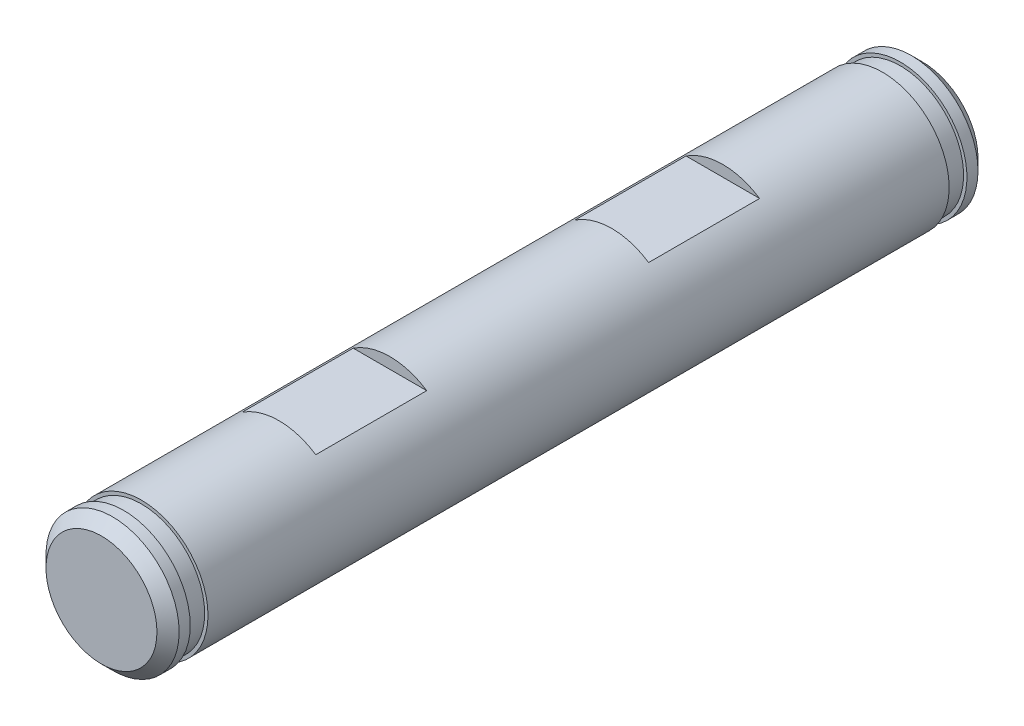
SolidWorks part; units mm, degrees
other "Uwaga1"
sketch "Szkic5" plane through (-3, 3, 37) normal (-0.9422, 0.1287, 0.3092) x (0.3037, -0.0607, 0.9508)
material "Stop 1060"
ref_plane "Płaszczyzna przednia" through (0, 0, 0) normal (0, 0, 1) x (1, 0, 0)
ref_plane "Płaszczyzna górna" through (0, 0, 0) normal (0, 1, 0) x (1, 0, 0)
ref_plane "Płaszczyzna prawa" through (0, 0, 0) normal (1, 0, 0) x (0, 0, -1)
sketch "Szkic1" plane through (0, 0, 0) normal (0, 0, 1) x (1, 0, 0)
  circle A0 centre (0, 0) radius 3
  dimension "D1" = 6
extrude "Dodanie-wyciągnięcie1" add sketch "Szkic1" along normal blind 37
chamfer "Sfazowanie1" distance 0.5 angle 45 2 edges at (3, 0, 0) (3, 0, 37)
sketch "Szkic2" plane through (0, 0, 37) normal (0, 0, 1) x (1, 0, 0)
  circle A0 centre (0, 0) radius 3
  circle A1 centre (0, 0) radius 2.85
  dimension "D1" = 6
  dimension "D2" = 5.7
extrude "Wytnij-wyciągnięcie1" cut sketch "Szkic2" against normal blind 0.8 from offset 1 offset against normal yes
sketch "Szkic3" plane through (0, 0, 0) normal (0, 0, -1) x (-1, 0, 0)
  circle A0 centre (0, 0) radius 3
  circle A1 centre (0, 0) radius 2.85
  dimension "D1" = 5.7
  dimension "D2" = 6
extrude "Wytnij-wyciągnięcie2" cut sketch "Szkic3" against normal blind 0.8 from offset 1 offset against normal yes
sketch "Szkic4" plane through (0, 0, 37) normal (0, 0, 1) x (1, 0, 0)
  line L0 (-1.6583, 2.5) -> (1.6583, 2.5)
  arc A0 (1.6583, 2.5) -> (-1.6583, 2.5) centre (0, 0) ccw
  dimension "D1" = 6
  dimension "D2" = 2.5
extrude "Wytnij-wyciągnięcie3" cut sketch "Szkic4" along normal blind 5 from offset 13 offset against normal yes
extrude "Wytnij-wyciągnięcie4" cut sketch "Szkic4<2>" against normal blind 5 from offset 23 offset against normal yes
sketch "Szkic4<2>" plane through (0, 0, 37) normal (0, 0, 1) x (1, 0, 0) same geometry as "Szkic4"
